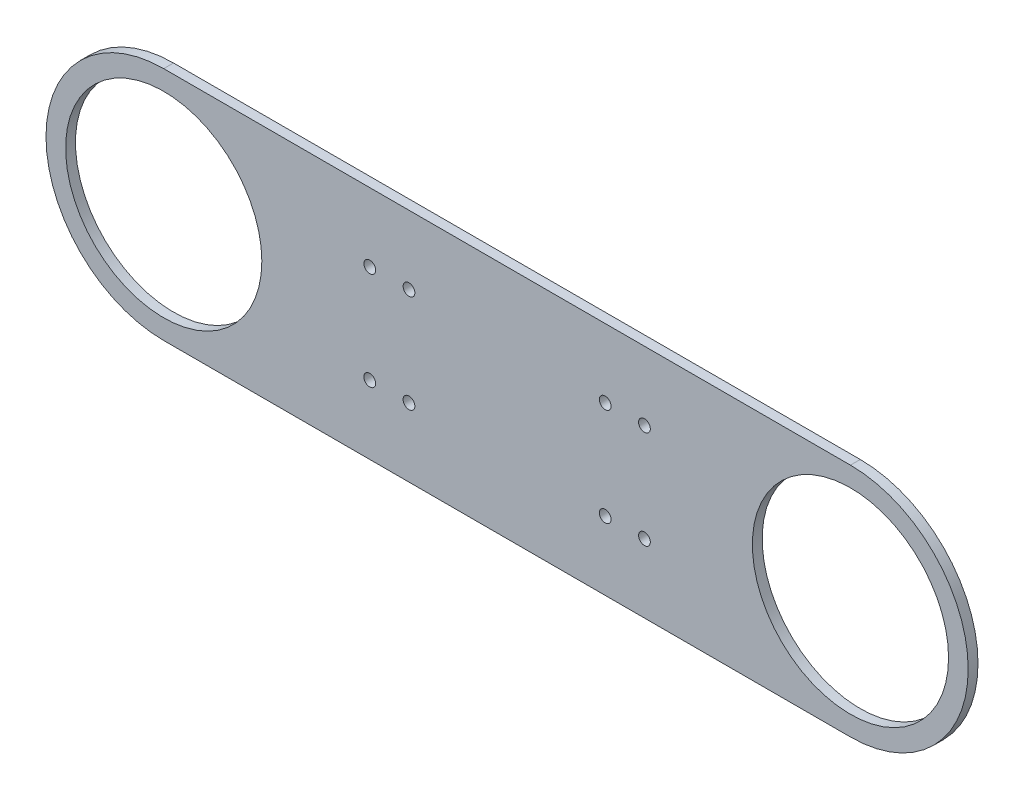
SolidWorks part; units mm, degrees
ref_plane "前视基准面" through (0, 0, 0) normal (0, 0, 1) x (1, 0, 0)
ref_plane "上视基准面" through (0, 0, 0) normal (0, 1, 0) x (1, 0, 0)
ref_plane "右视基准面" through (0, 0, 0) normal (1, 0, 0) x (0, 0, -1)
sketch "草图2" plane through (0, 0, 0) normal (0, 0, 1) x (1, 0, 0)
  line L0 (0, 0) -> (350, 0) construction
  line L1 (0, 60) -> (350, 60)
  line L2 (0, -60) -> (350, -60)
  arc A0 (0, 60) -> (0, -60) centre (0, 0) ccw
  arc A1 (350, -60) -> (350, 60) centre (350, 0) ccw
  circle A2 centre (0, 0) radius 50
  circle A3 centre (350, 0) radius 50
  point P3 (175, 0)
  dimension "D1" = 60
  dimension "D3" = 100
  dimension "D4" = 100
  dimension "D2" = 350
base flange "基体-法兰1" sketch "草图2" thickness 5 reverse thickness direction no parameters "D1"=10
sketch "草图3" plane through (0, 0, 0) normal (0, 0, 1) x (1, 0, 0)
  line L0 (0, 0) -> (350, 0) construction
  circle A0 centre (225, 25) radius 3
  circle A1 centre (245, 25) radius 3
  point P8 (175, 0)
  dimension "D1" = 6
  dimension "D2" = 6
  dimension "D3" = 20
  dimension "D4" = 50
  dimension "D5" = 25
extrude "切除-拉伸1" cut sketch "草图3" against normal blind 10 normal cut yes
mirror "镜向1" about plane through (0, 0, 0) normal (0, 1, 0) of "切除-拉伸1"
ref_plane "基准面1" through (175, 0, 0) normal (1, 0, 0) x (0, 0, -1)
mirror "镜向2" about plane through (175, 0, 0) normal (1, 0, 0) of "镜向1", "切除-拉伸1"
sketch "折弯-线1" [suppressed] plane through (0, 0, 0) normal (0, 1, 0) x (1, 0, 0)
sketch "边界框1" [suppressed] plane through (0, 0, 0) normal (0, 1, 0) x (1, 0, 0)
sheet metal parameters "钣金1" thickness 5 parameters "D1"=10
flat pattern "平板型式1" [suppressed]
sketch "折弯-线2" plane through (0, 0, 0) normal (0, 1, 0) x (1, 0, 0)
sketch3d "边界框2" [suppressed]
  line L0 (59.1405, 60.8474, 0) -> (-410.8474, 54.1615, 0) construction
  line L1 (60.8474, -59.1405, 0) -> (-409.1405, -65.8264, 0) construction
  line L2 (59.1405, 60.8474, 0) -> (60.8474, -59.1405, 0) construction
  line L3 (-410.8474, 54.1615, 0) -> (-409.1405, -65.8264, 0) construction
sheet metal parameters "钣金2" thickness 5 parameters "D1"=10
flat pattern "平板型式1"
sketch "折弯-线2" plane through (0, 0, 0) normal (0, 1, 0) x (1, 0, 0)
sketch3d "边界框2" [suppressed]
  line L0 (-59.1405, 60.8474, 0) -> (410.8474, 54.1615, 0) construction
  line L1 (-60.8474, -59.1405, 0) -> (409.1405, -65.8264, 0) construction
  line L2 (-59.1405, 60.8474, 0) -> (-60.8474, -59.1405, 0) construction
  line L3 (410.8474, 54.1615, 0) -> (409.1405, -65.8264, 0) construction
sheet metal parameters "钣金3" thickness 5 parameters "D1"=10
flat pattern "平板型式1"
sketch "折弯-线2" plane through (0, 0, 0) normal (0, 1, 0) x (1, 0, 0)
sketch3d "边界框2" [suppressed]
  line L0 (-59.1405, 60.8474, 0) -> (410.8474, 54.1615, 0) construction
  line L1 (-60.8474, -59.1405, 0) -> (409.1405, -65.8264, 0) construction
  line L2 (-59.1405, 60.8474, 0) -> (-60.8474, -59.1405, 0) construction
  line L3 (410.8474, 54.1615, 0) -> (409.1405, -65.8264, 0) construction
sheet metal parameters "钣金4" thickness 5 parameters "D1"=10
flat pattern "平板型式1"
sketch "折弯-线2" plane through (0, 0, 0) normal (0, 1, 0) x (1, 0, 0)
sketch3d "边界框2" [suppressed]
  line L0 (-60, 60, 0) -> (410, 60, 0) construction
  line L1 (-60, -60, 0) -> (410, -60, 0) construction
  line L2 (-60, 60, 0) -> (-60, -60, 0) construction
  line L3 (410, 60, 0) -> (410, -60, 0) construction
